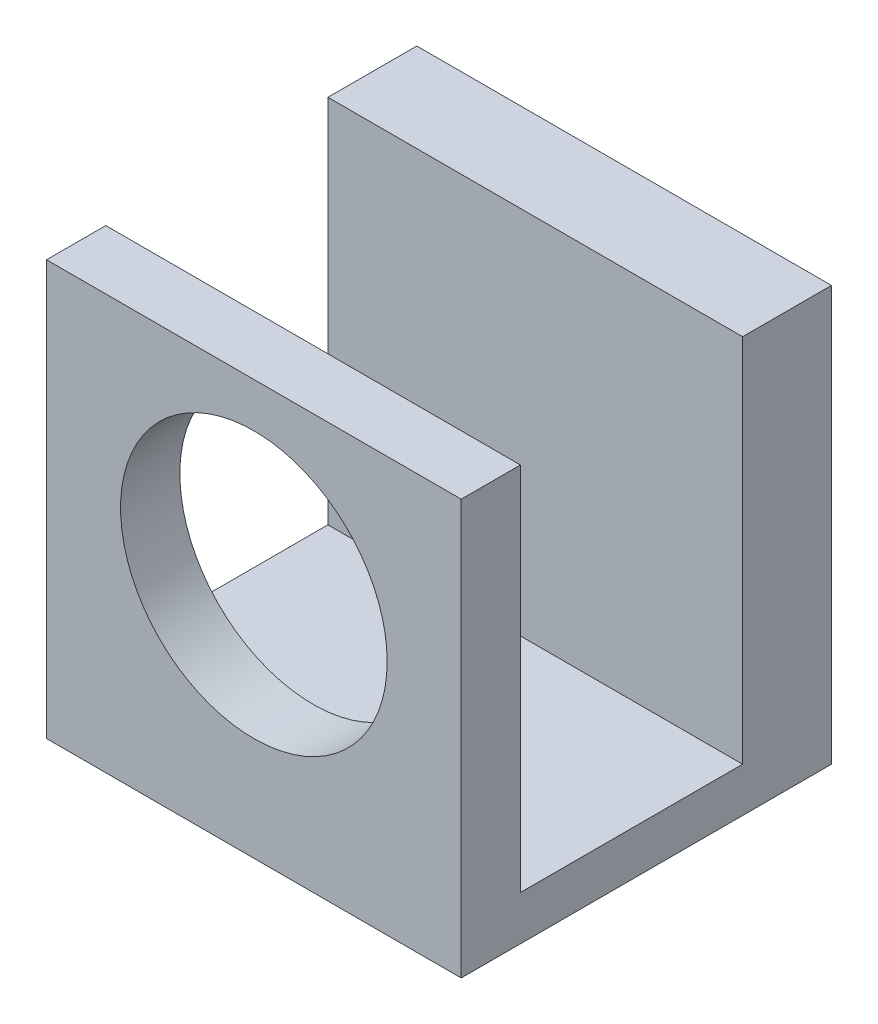
SolidWorks part; units mm, degrees
ref_plane "Front Plane" through (0, 0, 0) normal (0, 0, 1) x (1, 0, 0)
ref_plane "Top Plane" through (0, 0, 0) normal (0, 1, 0) x (1, 0, 0)
ref_plane "Right Plane" through (0, 0, 0) normal (1, 0, 0) x (0, 0, -1)
sketch "Sketch1" plane through (0, 0, 0) normal (0, 1, 0) x (1, 0, 0)
  line L1 (0, 0) -> (7.112, 0)
  line L2 (0, 0) -> (0, 6.35)
  line L3 (0, 6.35) -> (7.112, 6.35)
  line L4 (7.112, 0) -> (7.112, 6.35)
  dimension "D1" = 6.35
  dimension "D2" = 7.112
extrude "Boss-Extrude1" add sketch "Sketch1" along normal blind 7.112
sketch "Sketch2" plane through (0, 0, 0) normal (0, 0, 1) x (1, 0, 0)
  line L0 (0, 7.112) -> (0, 0) construction
  line L1 (0, 0) -> (7.112, 0) construction
  circle A0 centre (3.556, 4.064) radius 2.286
  dimension "D1" = 4.572
  dimension "D2" = 3.556
  dimension "D3" = 4.064
extrude "Cut-Extrude1" cut sketch "Sketch2" against normal blind 1.27
sketch "Sketch3" plane through (0, 7.112, 0) normal (0, 1, 0) x (1, 0, 0)
  line L1 (-2.54, 4.826) -> (8.89, 4.826)
  line L2 (-2.54, 4.826) -> (-2.54, 1.016)
  line L3 (-2.54, 1.016) -> (8.89, 1.016)
  line L4 (8.89, 4.826) -> (8.89, 1.016)
  line L5 (7.112, 6.35) -> (0, 6.35) construction
  line L6 (0, 6.35) -> (0, 0) construction
  dimension "D1" = 3.81
  dimension "D2" = 11.43
  dimension "D3" = 2.54
  dimension "D4" = 1.524
extrude "Cut-Extrude2" cut sketch "Sketch3" against normal blind 6.35 contours L2 L1 L4 L3
